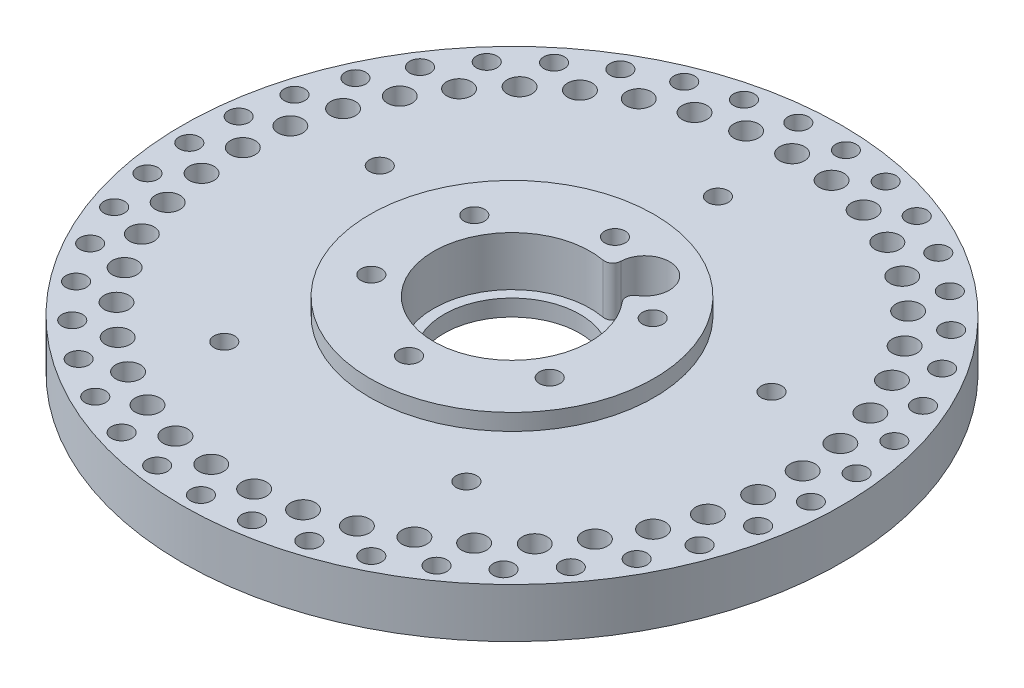
SolidWorks part; units mm, degrees
material "6061 Alloy"
ref_plane "Front Plane" through (0, 0, 0) normal (0, 0, 1) x (1, 0, 0)
ref_plane "Top Plane" through (0, 0, 0) normal (0, 1, 0) x (1, 0, 0)
ref_plane "Right Plane" through (0, 0, 0) normal (1, 0, 0) x (0, 0, -1)
sketch "Sketch1" plane through (0, 0, 0) normal (0, 1, 0) x (1, 0, 0)
  circle A0 centre (0, 0) radius 40
  dimension "D1" = 80
extrude "podstawa" add sketch "Sketch1" along normal blind 6
sketch "Sketch2" plane through (0, 6, 0) normal (0, 1, 0) x (1, 0, 0)
  circle A0 centre (0, 0) radius 9.5
  dimension "D1" = 19
extrude "gniazdo lozyska" cut sketch "Sketch2" against normal up to next and the other way through all
hole_wizard "walki cykloidy" positions "Sketch3" profile "Sketch5" hole size "Ø3.0" standard "DIN" end condition up to next
sketch "Sketch3" plane through (0, 6, 0) normal (0, 1, 0) x (1, 0, 0)
  line L0 (0, 34) -> (0, 40) construction
  circle A0 centre (0, 0) radius 40 construction
  point P0 (0, 34)
  point P15 (5.1901, 33.6015)
  point P16 (10.2585, 32.4155)
  point P17 (15.0865, 30.4696)
  point P18 (19.5608, 27.8096)
  point P19 (23.5767, 24.4977)
  point P20 (27.04, 20.6117)
  point P21 (29.8694, 16.2425)
  point P22 (31.9988, 11.4926)
  point P23 (33.3781, 6.4733)
  point P24 (33.9751, 1.3023)
  point P25 (33.7757, -3.8992)
  point P26 (32.7846, -9.0094)
  point P27 (31.0251, -13.9083)
  point P28 (28.5384, -18.4813)
  point P29 (25.3828, -22.6211)
  point P30 (21.6322, -26.2306)
  point P31 (17.3746, -29.2254)
  point P32 (12.7098, -31.5351)
  point P33 (7.747, -33.1056)
  point P34 (2.6027, -33.9002)
  point P35 (-2.6027, -33.9002)
  point P36 (-7.747, -33.1056)
  point P37 (-12.7098, -31.5351)
  point P38 (-17.3746, -29.2254)
  point P39 (-21.6322, -26.2306)
  point P40 (-25.3828, -22.6211)
  point P41 (-28.5384, -18.4813)
  point P42 (-31.0251, -13.9083)
  point P43 (-32.7846, -9.0094)
  point P44 (-33.7757, -3.8992)
  point P45 (-33.9751, 1.3023)
  point P46 (-33.3781, 6.4733)
  point P47 (-31.9988, 11.4926)
  point P48 (-29.8694, 16.2425)
  point P49 (-27.04, 20.6117)
  point P63 (-23.5767, 24.4977)
  point P64 (-19.5608, 27.8096)
  point P65 (-15.0865, 30.4696)
  point P66 (-10.2585, 32.4155)
  point P67 (-5.1901, 33.6015)
  dimension "D1" = 6
  dimension "D2" = 41
sketch "Sketch5" plane through (0, 6, -34) normal (1, 0, 0) x (0, 0, 1)
  line L0 (0, 0) -> (0, 6)
  line L1 (0, 6) -> (1.5, 6)
  line L2 (1.5, 6) -> (1.5, 0)
  line L5 (1.5, 0) -> (0, 0)
  line L11 (0, -6.35) -> (0, 107.95) construction
  dimension "Thru Hole Dia." = 3
  dimension "Thru Hole Depth" = 6
hole_wizard "Tap Drill for M3 Tap1" positions "Sketch7" profile "Sketch8" hole size "M3" standard "DIN" end condition up to next
sketch "Sketch7" plane through (0, 6, 0) normal (0, 1, 0) x (1, 0, 0)
  line L0 (0, 0) -> (0, 34)
  line L2 (0, 0) -> (5.1901, 33.6015)
  line L4 (5.1901, 33.6015) -> (0, 34)
  line L6 (3.2233, 41.9837) -> (0, 0)
  circle A0 centre (0, 0) radius 35.5
  circle A1 centre (0, 0) radius 40
  circle A3 centre (0, 0) radius 37.75 construction
  point P33 (2.8897, 37.6392)
  point P40 (8.6015, 36.757)
  point P41 (14.1116, 35.0132)
  point P42 (19.291, 32.4488)
  point P43 (24.0182, 29.1237)
  point P44 (28.1824, 25.116)
  point P45 (31.686, 20.5197)
  point P46 (34.447, 15.4423)
  point P47 (36.4006, 10.0031)
  point P48 (37.5009, 4.3293)
  point P49 (37.7223, -1.4459)
  point P50 (37.0595, -7.1873)
  point P51 (35.528, -12.7601)
  point P52 (33.1638, -18.0339)
  point P53 (30.0223, -22.885)
  point P54 (26.1771, -27.1997)
  point P55 (21.7183, -30.8768)
  point P56 (16.7504, -33.8302)
  point P57 (11.39, -35.9907)
  point P58 (5.7625, -37.3076)
  point P59 (0, -37.75)
  point P60 (-5.7625, -37.3076)
  point P61 (-11.39, -35.9907)
  point P62 (-16.7504, -33.8302)
  point P63 (-21.7183, -30.8768)
  point P64 (-26.1771, -27.1997)
  point P65 (-30.0223, -22.885)
  point P66 (-33.1638, -18.0339)
  point P67 (-35.528, -12.7601)
  point P68 (-37.0595, -7.1873)
  point P69 (-37.7223, -1.4459)
  point P70 (-37.5009, 4.3293)
  point P71 (-36.4006, 10.0031)
  point P72 (-34.447, 15.4423)
  point P73 (-31.686, 20.5197)
  point P74 (-28.1824, 25.116)
  point P75 (-24.0182, 29.1237)
  point P76 (-19.291, 32.4488)
  point P77 (-14.1116, 35.0132)
  point P78 (-8.6015, 36.757)
  point P79 (-2.8897, 37.6392)
  dimension "D1" = 80
  dimension "D2" = 71
  dimension "D3" = 75.5
  dimension "D4" = 41
sketch "Sketch8" plane through (-2.8897, 6, -37.6392) normal (1, 0, 0) x (0, 0, 1)
  line L0 (0, 0) -> (0, 6)
  line L1 (0, 6) -> (1.25, 6)
  line L2 (1.25, 6) -> (1.25, 0)
  line L5 (1.25, 0) -> (0, 0)
  line L11 (0, -6.35) -> (0, 107.95) construction
  dimension "Thru Hole Dia." = 2.5
  dimension "Thru Hole Depth" = 6
sketch "Sketch9" plane through (0, 0, 0) normal (0, 1, 0) x (1, 0, 0)
  circle A1 centre (0, 0) radius 9.5 construction
  circle A3 centre (0, 0) radius 8.25
  circle A4 centre (0, 0) radius 9.5
  dimension "D1" = 16.5
extrude "prog lozyska" add sketch "Sketch9" along normal blind 2
hole_wizard "Tap Drill for M3 Tap2" positions "Sketch10" profile "Sketch11" hole size "M3" standard "DIN" end condition up to next
sketch "Sketch10" plane through (0, 6, 0) normal (0, 1, 0) x (1, 0, 0)
  line L0 (0, 12.5) -> (0, 0)
  circle A0 centre (0, 12.5) radius 2.75
  circle A1 centre (0, 12.5) radius 3
  circle A3 centre (0, 0) radius 9.5 construction
  circle A4 centre (0, 0) radius 12.5
  point P0 (0, 12.5)
  point P16 (10.8253, 6.25)
  point P17 (10.8253, -6.25)
  point P45 (0, -12.5)
  point P46 (-10.8253, -6.25)
  point P47 (-10.8253, 6.25)
  dimension "D1" = 5.5
  dimension "D3" = 6
  dimension "D4" = 25
  dimension "D2" = 6
sketch "Sketch11" plane through (0, 6, -12.5) normal (1, 0, 0) x (0, 0, 1)
  line L0 (0, 0) -> (0, 6)
  line L1 (0, 6) -> (1.25, 6)
  line L2 (1.25, 6) -> (1.25, 0)
  line L5 (1.25, 0) -> (0, 0)
  line L11 (0, -6.35) -> (0, 107.95) construction
  dimension "Thru Hole Dia." = 2.5
  dimension "Thru Hole Depth" = 6
sketch "Sketch12" plane through (0, 6, 0) normal (0, 1, 0) x (1, 0, 0)
  line L0 (0, 12.5) -> (10.8253, 6.25) construction
  line L1 (0, 0) -> (9.7644, 16.9124) construction
  line L2 (4.75, 8.2272) -> (4.4, 7.621) construction
  circle A1 centre (5.9, 10.2191) radius 3
  circle A2 centre (0, 0) radius 9.5 construction
  dimension "D1" = 6
  dimension "D2" = 0.7
extrude "Cut-Extrude1" cut sketch "Sketch12" against normal up to surface (4 mm away) up to face at (0, 2, 9.5)
fillet "Fillet1" radius 1 2 edges at (6.1619, 4, -7.2306) (3.1809, 4, -8.9516)
hole_wizard "Tap Drill for M3 Tap3" positions "Sketch14" profile "Sketch15" hole size "M3" standard "DIN"
sketch "Sketch14" plane through (0, 6, 0) normal (0, 1, 0) x (1, 0, 0)
  point P0 (0, 25)
  point P9 (23.7764, 7.7254)
  point P10 (14.6946, -20.2254)
  point P11 (-14.6946, -20.2254)
  point P12 (-23.7764, 7.7254)
  dimension "D1" = 25
  dimension "D2" = 5
sketch "Sketch15" plane through (0, 6, -25) normal (1, 0, 0) x (0, 0, 1)
  line L0 (0, 0) -> (0, 6.7511)
  line L1 (0, 6.7511) -> (1.25, 6)
  line L2 (1.25, 6) -> (1.25, 0)
  line L5 (1.25, 0) -> (0, 0)
  line L10 (0, 6.7511) -> (-1.25, 6) construction
  line L11 (0, -6.35) -> (0, 107.95) construction
  dimension "Hole Dia." = 2.5
  dimension "Hole Depth" = 6
  dimension "Drill Angle" = 118
sketch "Sketch16" plane through (0, 6, 0) normal (0, 1, 0) x (1, 0, 0)
  circle A0 centre (0, 0) radius 17.25
  arc A1 (1.7203, 9.3429) -> (2.9011, 10.2996) centre (1.9014, 10.3264) ccw construction
  arc A2 (7.4692, 7.6622) -> (2.9011, 10.2996) centre (5.9, 10.2191) ccw construction
  arc A3 (7.4692, 7.6622) -> (7.231, 6.1613) centre (7.9922, 6.8099) ccw construction
  arc A4 (1.7203, 9.3429) -> (7.231, 6.1613) centre (0, 0) ccw construction
  circle A5 centre (10.8253, 6.25) radius 1.25 construction
  circle A6 centre (10.8253, -6.25) radius 1.25 construction
  circle A7 centre (0, -12.5) radius 1.25 construction
  circle A8 centre (-10.8253, -6.25) radius 1.25 construction
  circle A9 centre (-10.8253, 6.25) radius 1.25 construction
  circle A10 centre (0, 12.5) radius 1.25 construction
  arc A11 (1.7203, 9.3429) -> (2.9011, 10.2996) centre (1.9014, 10.3264) ccw
  arc A12 (7.4692, 7.6622) -> (2.9011, 10.2996) centre (5.9, 10.2191) ccw
  arc A13 (7.4692, 7.6622) -> (7.231, 6.1613) centre (7.9922, 6.8099) ccw
  arc A14 (1.7203, 9.3429) -> (7.231, 6.1613) centre (0, 0) ccw
  circle A15 centre (10.8253, 6.25) radius 1.25
  circle A16 centre (10.8253, -6.25) radius 1.25
  circle A17 centre (0, -12.5) radius 1.25
  circle A18 centre (-10.8253, -6.25) radius 1.25
  circle A19 centre (-10.8253, 6.25) radius 1.25
  circle A20 centre (0, 12.5) radius 1.25
  dimension "D1" = 34.5
extrude "Boss-Extrude1" add sketch "Sketch16" along normal blind 2
equation "\"D3@Sketch7\"=(\"D2@Sketch7\"+\"D1@Sketch7\")/2"
